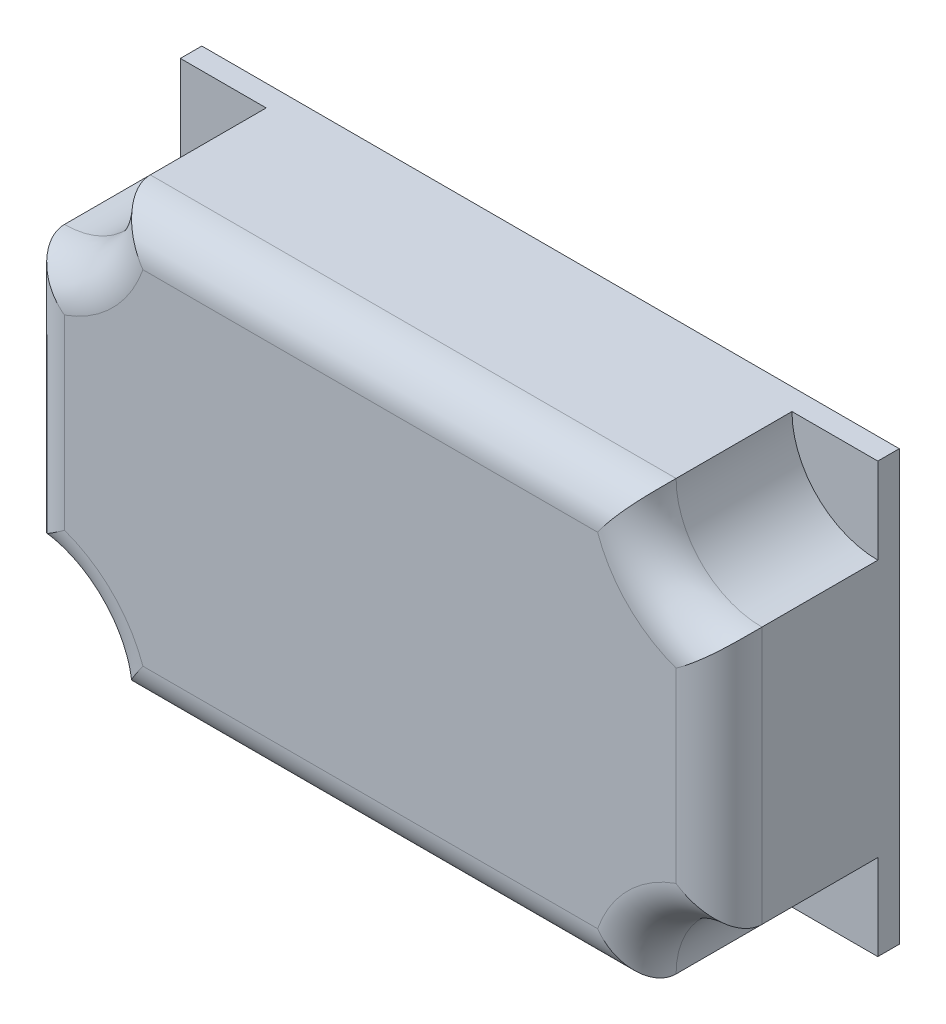
SolidWorks part; units mm, degrees
ref_plane "Front Plane" through (0, 0, 0) normal (0, 0, 1) x (1, 0, 0)
ref_plane "Top Plane" through (0, 0, 0) normal (0, 1, 0) x (1, 0, 0)
ref_plane "Right Plane" through (0, 0, 0) normal (1, 0, 0) x (0, 0, -1)
sketch "Sketch1" plane through (0, 0, 0) normal (0, 0, 1) x (1, 0, 0)
  line L0 (-37.1584, 21.8047) -> (-37.1584, -18.1953)
  line L1 (-37.1584, -18.1953) -> (27.8416, -18.1953)
  line L2 (27.8416, -18.1953) -> (27.8416, 21.8047)
  line L3 (27.8416, 21.8047) -> (-37.1584, 21.8047)
  arc A0 (-29.1584, -18.1953) -> (-37.1584, -10.1953) centre (-37.1584, -18.1953) ccw
  arc A1 (-29.1584, 21.8047) -> (-37.1584, 13.8047) centre (-37.1584, 21.8047) cw
  arc A2 (27.8416, 13.8047) -> (19.8416, 21.8047) centre (27.8416, 21.8047) cw
  arc A3 (27.8416, -10.1953) -> (19.8416, -18.1953) centre (27.8416, -18.1953) ccw
  dimension "D1" = 8
  dimension "D4" = 8
  dimension "D5" = 8
  dimension "D6" = 8
  dimension "D2" = 65
  dimension "D3" = 40
extrude "Boss-Extrude1" add sketch "Sketch1" along normal blind 14.8 contours A3 L2 A2 L3 A1 L0 A0 L1 region at (-4.6584, 1.8047, 0)
extrude "Boss-Extrude2" add sketch "Sketch1<3>" against normal blind 2 contours A2 L2 L3 | A1 L3 L0 | L2 A3 L1 | L1 A0 L0 | A3 L2 A2 L3 A1 L0 A0 L1 region at (-33.763, 18.4094, 0) region at (-4.6584, 1.8047, 0) region at (-33.763, -14.8, 0) region at (24.4463, 18.4094, 0) region at (24.4463, -14.8, 0)
sketch "Sketch1<3>" plane through (0, 0, 0) normal (0, 0, 1) x (1, 0, 0) same geometry as "Sketch1"
fillet "Fillet1" radius 4 8 edges at (-4.6584, -18.1953, 14.8) (-31.5015, -12.5384, 14.8) (-37.1584, 1.8047, 14.8) (-31.5015, 16.1479, 14.8) (-4.6584, 21.8047, 14.8) (22.1848, 16.1479, 14.8) (27.8416, 1.8047, 14.8) (22.1848, -12.5384, 14.8)
